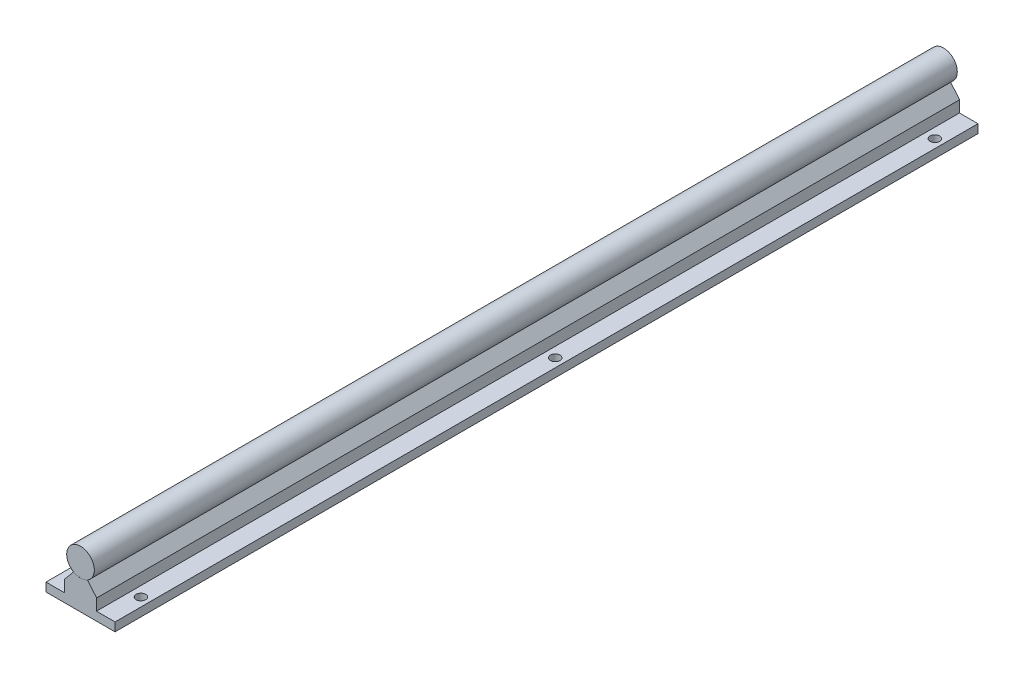
SolidWorks part; units mm, degrees
note: '?' marks a value the reader was unsure of.
material "Chrome Stainless Steel"
ref_plane "Front" through (0, 0, 0) normal (0, 0, 1) x (1, 0, 0)
ref_plane "Top" through (0, 0, 0) normal (0, 1, 0) x (1, 0, 0)
ref_plane "Right" through (0, 0, 0) normal (1, 0, 0) x (0, 0, -1)
ref_axis "Axis1" through (-84.4107, 0, 0) along (1, 0, 0)?
ref_axis "Axis2" through (0, 64.3378, 0) along (0, -1, 0)?
ref_axis "Axis3" through (0, 0, -102.329) along (0, 0, 1)?
sketch "Sketch1" plane through (0, 0, 0) normal (0, 0, 1) x (1, 0, 0)
  circle A0 centre (0, -1.8255) radius 8
  dimension "D1" = 16
extrude "Extrude1" add sketch "Sketch1" along normal blind 500
sketch "Sketch2" plane through (0, 0, 0) normal (0, 0, 1) x (1, 0, 0)
  line L0 (0, -8.7616) -> (0, -11.4511) construction
  line L1 (4, -8.7537) -> (9.3466, -15.1255)
  line L3 (9.25, -21.8255) -> (20, -21.8255)
  line L4 (20, -21.8255) -> (20, -26.8255)
  line L5 (20, -26.8255) -> (0, -26.8255)
  line L6 (0, -26.8255) -> (0, -9.8255)
  line L7 (0, -11.4511) -> (0, -13.4825) construction
  line L8 (9.3466, -15.1255) -> (9.25, -15.1255)
  line L9 (9.25, -15.1255) -> (9.25, -21.8255)
  arc A0 (0, -9.8255) -> (4, -8.7537) centre (0, -1.8255) ccw
  circle A1 centre (0, -1.8255) radius 8 construction
  circle A2 centre (0, -1.8255) radius 8 construction
  dimension "D1" = 4
  dimension "D2" = 40
  dimension "D3" = 5
  dimension "D4" = 11.7
  dimension "D5" = 9.25
  dimension "D6" = 25
  dimension "D7" = 20
extrude "Extrude3" add sketch "Sketch2" along normal blind 500 separate body
mirror "Mirror5" about plane through (0, -26.8255, 500) normal (1, 0, 0) of bodies 103
hole_wizard "M5 Tapped Hole2" [suppressed] positions "Sketch6" profile "Sketch7" tap size "M5" standard "ISO"
sketch "Sketch6" [suppressed] plane through (0, -21.5537, 0) normal (0, 1, 0) x (-1, 0, 0)
  line L0 (-20, 0) -> (-9.25, 0) construction
  line L1 (0, 50) -> (0, -50) construction
  point P0 (-15, 25)
  dimension "D1" = 25
  dimension "D2" = 15
sketch "Sketch7" [suppressed] plane through (15, -21.5537, 25) normal (1, 0, 0) x (0, 0, 1)
  line L0 (0, 0) -> (0, 5)
  line L1 (0, 5) -> (2.1, 5)
  line L2 (2.1, 5) -> (2.1, 0)
  line L5 (2.1, 0) -> (0, 0)
  line L11 (0, -6.35) -> (0, 107.95) construction
  dimension "Thru Tap Drill Dia." = 4.2
  dimension "Thru Tap Drill Depth" = 5
cosmetic thread "Hole Thread2" parameters "D2"=5
combine bodies "Combine1" operation type add bodies to combine 105 103
sketch "Sketch8" plane through (0, -26.8255, 0) normal (0, -1, 0) x (1, 0, 0)
  line L0 (0, -24.7558) -> (0, 504.6317) construction
  line L1 (38.9599, 480) -> (-38.5377, 480) construction
  line L2 (48.3999, 20) -> (-45.4541, 20) construction
  line L3 (20, 0) -> (-20, 0) construction
  line L4 (20, 500) -> (-20, 500) construction
  line L5 (-25.9366, 239.9379) -> (25.1299, 239.9379) construction
  circle A0 centre (-15, 20) radius 2.75
  circle A1 centre (15, 20) radius 2.75
  circle A2 centre (-15, 239.9379) radius 2.75
  circle A3 centre (15, 239.9379) radius 2.75
  circle A4 centre (-15, 480) radius 2.75
  circle A5 centre (15, 480) radius 2.75
  dimension "D3" = 5.5
  dimension "D4" = 5.5
  dimension "D5" = 15
  dimension "D6" = 15
  dimension "D7" = 5.5
  dimension "D8" = 5.5
  dimension "D9" = 15
  dimension "D10" = 15
  dimension "D11" = 5.5
  dimension "D12" = 5.5
  dimension "D13" = 15
  dimension "D14" = 15
  dimension "D1" = 20
  dimension "D2" = 20
extrude "Cut-Extrude1" cut sketch "Sketch8" against normal up to next (5 mm away)
